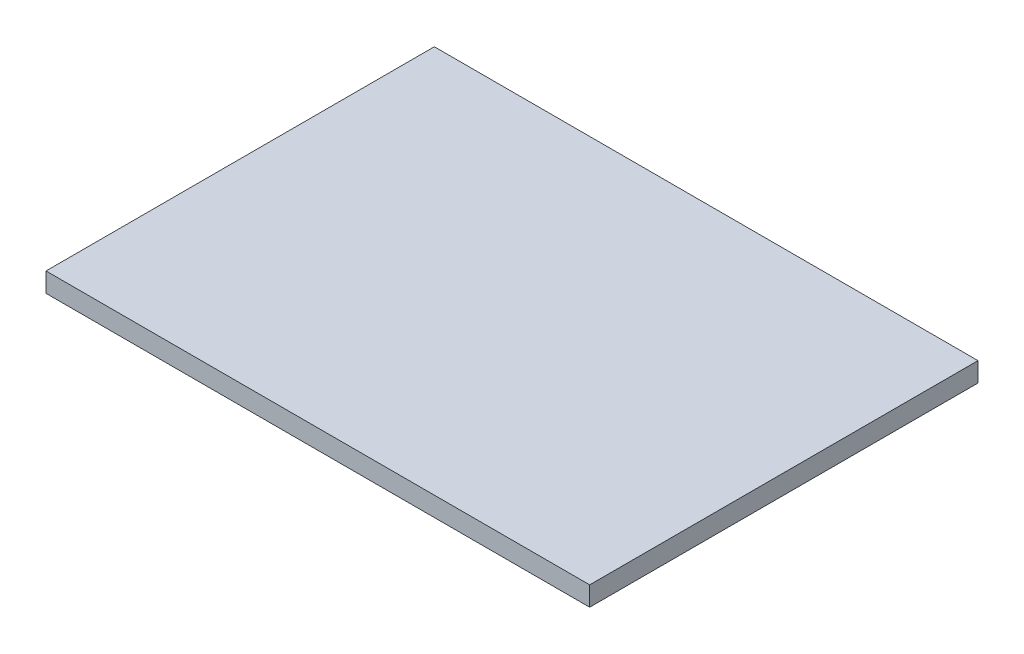
SolidWorks part; units mm, degrees
material "Alloy Steel (SS)"
ref_plane "Front Plane" through (0, 0, 0) normal (0, 0, 1) x (1, 0, 0)
ref_plane "Top Plane" through (0, 0, 0) normal (0, 1, 0) x (1, 0, 0)
ref_plane "Right Plane" through (0, 0, 0) normal (1, 0, 0) x (0, 0, -1)
sketch "Sketch1" plane through (0, 0, 0) normal (0, 1, 0) x (1, 0, 0)
  line L1 (0, 762) -> (711.2, 762)
  line L2 (0, 762) -> (0, 254)
  line L3 (0, 254) -> (711.2, 254)
  line L4 (711.2, 762) -> (711.2, 254)
  dimension "D1" = 711.2
  dimension "D2" = 508
extrude "Boss-Extrude1" add sketch "Sketch1" along normal blind 25.4
